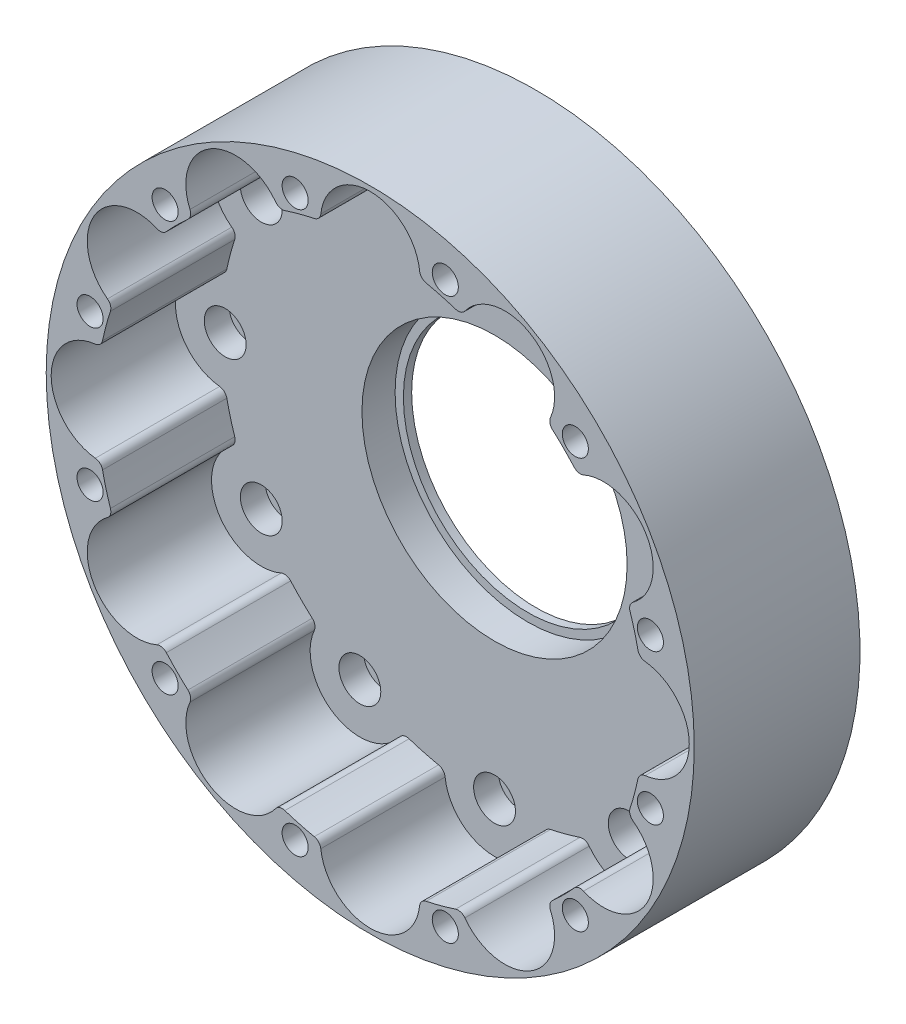
SolidWorks part; units mm, degrees
material "ABS"
ref_plane "Front Plane" through (0, 0, 0) normal (0, 0, 1) x (1, 0, 0)
ref_plane "Top Plane" through (0, 0, 0) normal (0, 1, 0) x (1, 0, 0)
ref_plane "Right Plane" through (0, 0, 0) normal (1, 0, 0) x (0, 0, -1)
sketch "Sketch1" plane through (0, 0, 0) normal (0, 0, 1) x (1, 0, 0)
  circle A0 centre (0, 0) radius 39.1
  circle A1 centre (0, 0) radius 32.5 construction
  circle A2 centre (32.5, 0) radius 2.525
  circle A3 centre (28.1458, -16.25) radius 2.525
  circle A4 centre (16.25, -28.1458) radius 2.525
  circle A5 centre (0, -32.5) radius 2.525
  circle A6 centre (-16.25, -28.1458) radius 2.525
  circle A7 centre (-28.1458, -16.25) radius 2.525
  circle A8 centre (-32.5, 0) radius 2.525
  circle A9 centre (-28.1458, 16.25) radius 2.525
  circle A10 centre (-16.25, 28.1458) radius 2.525
  circle A11 centre (0, 32.5) radius 2.525
  circle A12 centre (16.25, 28.1458) radius 2.525
  circle A13 centre (0, 0) radius 16
  circle A14 centre (28.1458, 16.25) radius 2.525
  point P28 (0, 0)
extrude "Boss-Extrude1" add sketch "Sketch1" along normal blind 3
sketch "Sketch2" plane through (0, 0, 0) normal (0, 0, -1) x (-1, 0, 0)
  circle A0 centre (0, 0) radius 16
  circle A1 centre (0, 0) radius 39.1
  circle A2 centre (0, 0) radius 39.1 construction
  dimension "D1" = 32
extrude "Boss-Extrude2" add sketch "Sketch2" along normal blind 2 contours A1 | A0
sketch "Sketch3" plane through (0, 0, 3) normal (0, 0, 1) x (1, 0, 0)
  circle A0 centre (32.5, 0) radius 1.6
  circle A1 centre (28.1458, -16.25) radius 1.6
  circle A2 centre (16.25, -28.1458) radius 1.6
  circle A3 centre (0, -32.5) radius 1.6
  circle A4 centre (-16.25, -28.1458) radius 1.6
  circle A5 centre (-28.1458, -16.25) radius 1.6
  circle A6 centre (-32.5, 0) radius 1.6
  circle A7 centre (-28.1458, 16.25) radius 1.6
  circle A8 centre (-16.25, 28.1458) radius 1.6
  circle A9 centre (0, 32.5) radius 1.6
  circle A10 centre (16.25, 28.1458) radius 1.6
  circle A11 centre (28.1458, 16.25) radius 1.6
  point P25 (0, 0)
  dimension "D1" = 3.2
  dimension "D2" = 12
sketch "Sketch4" plane through (0, 0, -2) normal (0, 0, -1) x (-1, 0, 0)
  circle A0 centre (0, 0) radius 16
  circle A1 centre (0, 0) radius 15
  dimension "D1" = 32
  dimension "D2" = 30
extrude "Boss-Extrude3" add sketch "Sketch4" against normal blind 1
sketch "Sketch5" plane through (0, 0, 3) normal (0, 0, 1) x (1, 0, 0)
  circle A0 centre (0, 0) radius 39.1
  circle A1 centre (0, 0) radius 39.1 construction
  arc A2 (-11.029, 31.1024) -> (-21.421, 25.1026) centre (-16.25, 28.1458) ccw
  arc A3 (5.9998, 32.45) -> (-5.9998, 32.45) centre (0, 32.5) ccw
  arc A4 (21.421, 25.1026) -> (11.029, 31.1024) centre (16.25, 28.1458) ccw
  arc A5 (31.1024, 11.029) -> (25.1026, 21.421) centre (28.1458, 16.25) ccw
  arc A6 (32.45, -5.9998) -> (32.45, 5.9998) centre (32.5, 0) ccw
  arc A7 (25.1026, -21.421) -> (31.1024, -11.029) centre (28.1458, -16.25) ccw
  arc A8 (11.029, -31.1024) -> (21.421, -25.1026) centre (16.25, -28.1458) ccw
  arc A9 (-5.9998, -32.45) -> (5.9998, -32.45) centre (0, -32.5) ccw
  arc A10 (-21.421, -25.1026) -> (-11.029, -31.1024) centre (-16.25, -28.1458) ccw
  arc A11 (-31.1024, -11.029) -> (-25.1026, -21.421) centre (-28.1458, -16.25) ccw
  arc A12 (-32.45, 5.9998) -> (-32.45, -5.9998) centre (-32.5, 0) ccw
  arc A13 (-25.1026, -21.421) -> (-21.421, -25.1026) centre (0, 0) ccw
  arc A14 (-32.45, -5.9998) -> (-31.1024, -11.029) centre (0, 0) ccw
  arc A15 (-21.421, 25.1026) -> (-25.1026, 21.421) centre (0, 0) ccw
  arc A16 (-5.9998, 32.45) -> (-11.029, 31.1024) centre (0, 0) ccw
  arc A17 (11.029, 31.1024) -> (5.9998, 32.45) centre (0, 0) ccw
  arc A18 (25.1026, 21.421) -> (21.421, 25.1026) centre (0, 0) ccw
  arc A19 (32.45, 5.9998) -> (31.1024, 11.029) centre (0, 0) ccw
  arc A20 (31.1024, -11.029) -> (32.45, -5.9998) centre (0, 0) ccw
  arc A21 (21.421, -25.1026) -> (25.1026, -21.421) centre (0, 0) ccw
  arc A22 (5.9998, -32.45) -> (11.029, -31.1024) centre (0, 0) ccw
  arc A23 (-11.029, -31.1024) -> (-5.9998, -32.45) centre (0, 0) ccw
  arc A24 (-25.1026, 21.421) -> (-31.1024, 11.029) centre (-28.1458, 16.25) ccw
  arc A25 (-31.1024, 11.029) -> (-32.45, 5.9998) centre (0, 0) ccw
  point P30 (0, 0)
  dimension "D1" = 12
  dimension "D2" = 6
  dimension "D3" = 33
extrude "Boss-Extrude4" add sketch "Sketch5" along normal blind 15 contours A24 A15 A2 A0 | A16 A3 A0 A2 | A17 A4 A0 A3 | A18 A5 A0 A4 | A19 A6 A0 A5 | A20 A7 A0 A6 | A21 A8 A0 A7 | A22 A9 A0 A8 | A23 A10 A0 A9 | A13 A11 A0 A10 | A14 A12 A0 A11 | A24 A0 A12 A15 region at (-38.9894, 0, 3)
fillet "Fillet2" radius 1 24 edges at (11.029, -31.1024, 10.5) (5.9998, -32.45, 10.5) (32.45, -5.9998, 10.5) (31.1024, -11.029, 10.5) (25.1026, -21.421, 10.5) (21.421, -25.1026, 10.5) (-11.029, -31.1024, 10.5) (-5.9998, -32.45, 10.5) (-21.421, -25.1026, 10.5) (-25.1026, -21.421, 10.5) (-32.45, -5.9998, 10.5) (-31.1024, -11.029, 10.5) (-21.421, 25.1026, 10.5) (32.45, 5.9998, 10.5) (31.1024, 11.029, 10.5) (25.1026, 21.421, 10.5) (21.421, 25.1026, 10.5) (11.029, 31.1024, 10.5) (5.9998, 32.45, 10.5) (-5.9998, 32.45, 10.5) (-11.029, 31.1024, 10.5) (-32.45, 5.9998, 10.5) (-31.1024, 11.029, 10.5) (-25.1026, 21.421, 10.5)
sketch "Sketch7" plane through (0, 0, -2) normal (0, 0, -1) x (-1, 0, 0)
  line L0 (0, 0) -> (33.8074, -9.0587) construction
  line L1 (0, 0) -> (35, 0) construction
  circle A0 centre (33.8074, -9.0587) radius 1.575
  circle A1 centre (24.7487, -24.7487) radius 1.575
  circle A2 centre (9.0587, -33.8074) radius 1.575
  circle A3 centre (-9.0587, -33.8074) radius 1.575
  circle A4 centre (-24.7487, -24.7487) radius 1.575
  circle A5 centre (-33.8074, -9.0587) radius 1.575
  circle A6 centre (-33.8074, 9.0587) radius 1.575
  circle A7 centre (-24.7487, 24.7487) radius 1.575
  circle A8 centre (-9.0587, 33.8074) radius 1.575
  circle A9 centre (9.0587, 33.8074) radius 1.575
  circle A10 centre (24.7487, 24.7487) radius 1.575
  circle A11 centre (33.8074, 9.0587) radius 1.575
  point P26 (0, 0)
  dimension "D2" = 3.15
  dimension "D4" = 35
  dimension "D5" = 15
  dimension "D3" = 12
extrude "Cut-Extrude1" cut sketch "Sketch7" against normal through all
sketch "Sketch8" plane through (0, 0, -2) normal (0, 0, -1) x (-1, 0, 0)
  line L0 (27.5987, -26.3942) -> (27.5987, -23.1033)
  line L1 (37.0983, -9.0587) -> (35.4529, -6.2087)
  line L2 (35.4529, -6.2087) -> (32.162, -6.2087)
  line L3 (32.162, -6.2087) -> (30.5165, -9.0587)
  line L4 (30.5165, -9.0587) -> (32.162, -11.9087)
  line L5 (32.162, -11.9087) -> (35.4529, -11.9087)
  line L6 (35.4529, -11.9087) -> (37.0983, -9.0587)
  line L7 (27.5987, -23.1033) -> (24.7487, -21.4578)
  line L8 (24.7487, -21.4578) -> (21.8987, -23.1033)
  line L9 (21.8987, -23.1033) -> (21.8987, -26.3942)
  line L10 (21.8987, -26.3942) -> (24.7487, -28.0396)
  line L11 (24.7487, -28.0396) -> (27.5987, -26.3942)
  line L12 (10.7041, -36.6574) -> (12.3496, -33.8074)
  line L13 (12.3496, -33.8074) -> (10.7041, -30.9574)
  line L14 (10.7041, -30.9574) -> (7.4132, -30.9574)
  line L15 (7.4132, -30.9574) -> (5.7678, -33.8074)
  line L16 (5.7678, -33.8074) -> (7.4132, -36.6574)
  line L17 (7.4132, -36.6574) -> (10.7041, -36.6574)
  line L18 (-9.0587, -37.0983) -> (-6.2087, -35.4529)
  line L19 (-6.2087, -35.4529) -> (-6.2087, -32.162)
  line L20 (-6.2087, -32.162) -> (-9.0587, -30.5165)
  line L21 (-9.0587, -30.5165) -> (-11.9087, -32.162)
  line L22 (-11.9087, -32.162) -> (-11.9087, -35.4529)
  line L23 (-11.9087, -35.4529) -> (-9.0587, -37.0983)
  line L24 (-26.3942, -27.5987) -> (-23.1033, -27.5987)
  line L25 (-23.1033, -27.5987) -> (-21.4578, -24.7487)
  line L26 (-21.4578, -24.7487) -> (-23.1033, -21.8987)
  line L27 (-23.1033, -21.8987) -> (-26.3942, -21.8987)
  line L28 (-26.3942, -21.8987) -> (-28.0396, -24.7487)
  line L29 (-28.0396, -24.7487) -> (-26.3942, -27.5987)
  line L30 (-36.6574, -10.7041) -> (-33.8074, -12.3496)
  line L31 (-33.8074, -12.3496) -> (-30.9574, -10.7041)
  line L32 (-30.9574, -10.7041) -> (-30.9574, -7.4132)
  line L33 (-30.9574, -7.4132) -> (-33.8074, -5.7678)
  line L34 (-33.8074, -5.7678) -> (-36.6574, -7.4132)
  line L35 (-36.6574, -7.4132) -> (-36.6574, -10.7041)
  line L36 (-37.0983, 9.0587) -> (-35.4529, 6.2087)
  line L37 (-35.4529, 6.2087) -> (-32.162, 6.2087)
  line L38 (-32.162, 6.2087) -> (-30.5165, 9.0587)
  line L39 (-30.5165, 9.0587) -> (-32.162, 11.9087)
  line L40 (-32.162, 11.9087) -> (-35.4529, 11.9087)
  line L41 (-35.4529, 11.9087) -> (-37.0983, 9.0587)
  line L42 (-27.5987, 26.3942) -> (-27.5987, 23.1033)
  line L43 (-27.5987, 23.1033) -> (-24.7487, 21.4578)
  line L44 (-24.7487, 21.4578) -> (-21.8987, 23.1033)
  line L45 (-21.8987, 23.1033) -> (-21.8987, 26.3942)
  line L46 (-21.8987, 26.3942) -> (-24.7487, 28.0396)
  line L47 (-24.7487, 28.0396) -> (-27.5987, 26.3942)
  line L48 (-10.7041, 36.6574) -> (-12.3496, 33.8074)
  line L49 (-12.3496, 33.8074) -> (-10.7041, 30.9574)
  line L50 (-10.7041, 30.9574) -> (-7.4132, 30.9574)
  line L51 (-7.4132, 30.9574) -> (-5.7678, 33.8074)
  line L52 (-5.7678, 33.8074) -> (-7.4132, 36.6574)
  line L53 (-7.4132, 36.6574) -> (-10.7041, 36.6574)
  line L54 (9.0587, 37.0983) -> (6.2087, 35.4529)
  line L55 (6.2087, 35.4529) -> (6.2087, 32.162)
  line L56 (6.2087, 32.162) -> (9.0587, 30.5165)
  line L57 (9.0587, 30.5165) -> (11.9087, 32.162)
  line L58 (11.9087, 32.162) -> (11.9087, 35.4529)
  line L59 (11.9087, 35.4529) -> (9.0587, 37.0983)
  line L60 (26.3942, 27.5987) -> (23.1033, 27.5987)
  line L61 (23.1033, 27.5987) -> (21.4578, 24.7487)
  line L62 (21.4578, 24.7487) -> (23.1033, 21.8987)
  line L63 (23.1033, 21.8987) -> (26.3942, 21.8987)
  line L64 (26.3942, 21.8987) -> (28.0396, 24.7487)
  line L65 (28.0396, 24.7487) -> (26.3942, 27.5987)
  line L66 (36.6574, 10.7041) -> (33.8074, 12.3496)
  line L67 (33.8074, 12.3496) -> (30.9574, 10.7041)
  line L68 (30.9574, 10.7041) -> (30.9574, 7.4132)
  line L69 (30.9574, 7.4132) -> (33.8074, 5.7678)
  line L70 (33.8074, 5.7678) -> (36.6574, 7.4132)
  line L71 (36.6574, 7.4132) -> (36.6574, 10.7041)
  circle A0 centre (33.8074, -9.0587) radius 2.85 construction
  circle A1 centre (24.7487, -24.7487) radius 2.85 construction
  circle A2 centre (9.0587, -33.8074) radius 2.85 construction
  circle A3 centre (-9.0587, -33.8074) radius 2.85 construction
  circle A4 centre (-24.7487, -24.7487) radius 2.85 construction
  circle A5 centre (-33.8074, -9.0587) radius 2.85 construction
  circle A6 centre (-33.8074, 9.0587) radius 2.85 construction
  circle A7 centre (-24.7487, 24.7487) radius 2.85 construction
  circle A8 centre (-9.0587, 33.8074) radius 2.85 construction
  circle A9 centre (9.0587, 33.8074) radius 2.85 construction
  circle A10 centre (24.7487, 24.7487) radius 2.85 construction
  circle A11 centre (33.8074, 9.0587) radius 2.85 construction
  point P91 (0, 0)
  dimension "D1" = 5.7
  dimension "D2" = 12
extrude "Cut-Extrude3" cut sketch "Sketch8" against normal blind 3
sketch "Sketch9" plane through (0, 0, 3) normal (0, 0, 1) x (1, 0, 0)
  circle A0 centre (0, 0) radius 39.1
  circle A1 centre (0, 0) radius 38.5
  dimension "D1" = 77
equation "\"RingPinShaft\"= 5.05"
equation "\"CenterBearingOut\"=32.00"
equation "\"OutputBearingOut\"=50.00"
equation "\"RingPostIn\"=5.15"
equation "\"CamBearingOut\"=15.1"
equation "\"DiskOutputShaft\"=10.1"
equation "\"CenterShaft\"=25.2"
equation "\"Eccentricity\"=2"
equation "\"CycCamShaft\"=10.05"
equation "\"m3Thru\"=3.15"
equation "\"m3Insert\"=4.2"
equation "\"MountingHoleDiam\"=35"
equation "\"D2@Sketch7\"=\"m3Thru\""
equation "\"D4@Sketch7\"=\"MountingHoleDiam\""
